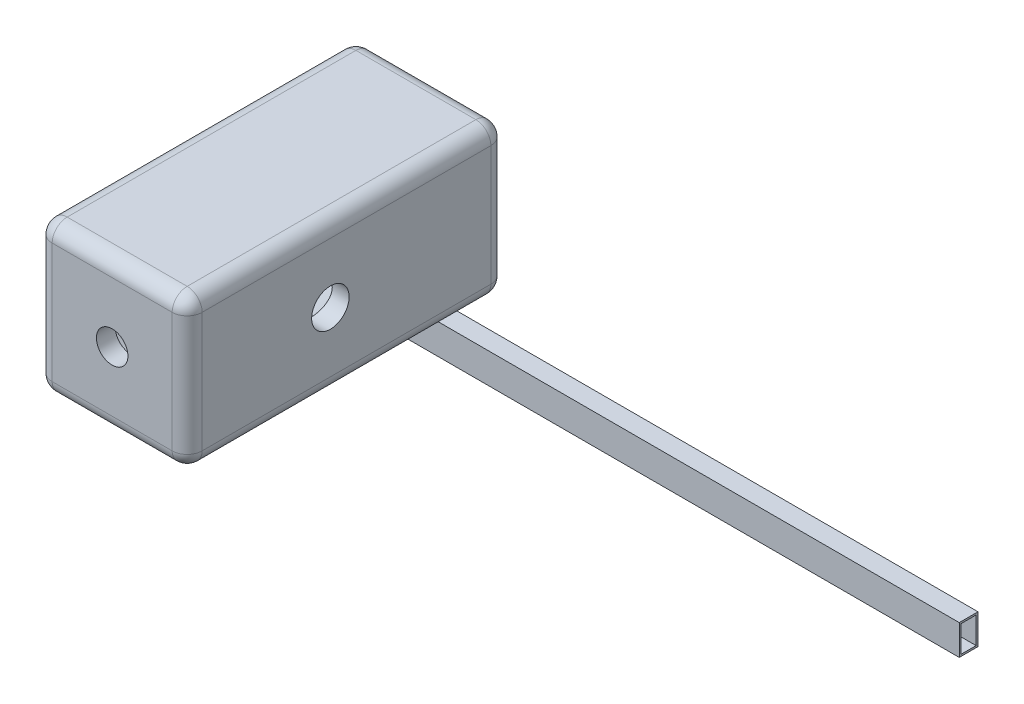
SolidWorks part; units mm, degrees
ref_plane "Front Plane" through (0, 0, 0) normal (0, 0, 1) x (1, 0, 0)
ref_plane "Top Plane" through (0, 0, 0) normal (0, 1, 0) x (1, 0, 0)
ref_plane "Right Plane" through (0, 0, 0) normal (1, 0, 0) x (0, 0, -1)
sketch "Sketch1" plane through (0, 0, 0) normal (0, 0, 1) x (1, 0, 0)
  line L1 (-25.4, 25.4) -> (25.4, 25.4)
  line L2 (-25.4, 25.4) -> (-25.4, -25.4)
  line L3 (-25.4, -25.4) -> (25.4, -25.4)
  line L4 (25.4, 25.4) -> (25.4, -25.4)
  line L5 (-25.4, 25.4) -> (25.4, -25.4) construction
  line L6 (-25.4, -25.4) -> (25.4, 25.4) construction
  point P0 (0, 0)
extrude "Boss-Extrude1" add sketch "Sketch1" against normal blind 101.6
sketch "Sketch3" plane through (0, 0, 0) normal (0, 0, 1) x (1, 0, 0)
  circle A0 centre (0, 0) radius 19.685
extrude "Cut-Extrude1" cut sketch "Sketch3" against normal blind 88.9 contours A0
sketch "Sketch6" plane through (0, 0, -101.6) normal (0, 0, -1) x (-1, 0, 0)
  line L1 (-7.62, 0) -> (-7.62, -25.4048)
  line L2 (7.62, 0) -> (7.62, -25.4048)
  line L5 (-7.62, -25.4048) -> (-7.62, -31.7548)
  line L6 (7.62, -25.4048) -> (7.62, -31.7548)
  line L7 (-7.62, -31.7548) -> (7.62, -31.7548)
  arc A0 (7.62, 0) -> (-7.62, 0) centre (0, 0) ccw
extrude "Boss-Extrude2" add sketch "Sketch6" along normal blind 10.16
sketch "Sketch11" plane through (0, 0, -88.9) normal (0, 0, 1) x (1, 0, 0)
  circle A0 centre (0, 0) radius 6.35
extrude "Cut-Extrude3" cut sketch "Sketch11" against normal blind 20.32
sketch "Sketch13" plane through (0, 0, 0) normal (0, 0, 1) x (1, 0, 0)
  line L1 (-25.4, 25.4) -> (25.4, 25.4)
  line L2 (-25.4, 25.4) -> (-25.4, -25.4)
  line L3 (-25.4, -25.4) -> (25.4, -25.4)
  line L4 (25.4, 25.4) -> (25.4, -25.4)
  circle A0 centre (0, 0) radius 5.334
extrude "Boss-Extrude4" add sketch "Sketch13" along normal blind 6.35
fillet "Fillet2" radius 5.08 4 edges at (-25.4, 0, -101.6) (-25.4, 25.4, -47.625) (-25.4, 0, 6.35) (-25.4, -25.4, -47.625)
fillet "Fillet5" radius 2.54 3 edges at (0, 7.62, -111.76) (7.62, -15.8774, -111.76) (-7.62, -15.8774, -111.76)
sketch "Sketch14" plane through (-25.4, 0, 0) normal (-1, 0, 0) x (0, 0, 1)
  line L0 (6.35, 25.4) -> (6.35, -25.4) construction
  circle A0 centre (-42.164, 0) radius 6.35
  dimension "D1" = 48.514
extrude "Cut-Extrude5" cut sketch "Sketch14" against normal through all both and the other way through all
fillet "Fillet8" radius 5.08 6 edges at (25.4, 0, -101.6) (2.54, -25.4, 6.35) (-23.9121, -23.9121, 4.8621) (-23.9121, 23.9121, -100.1121) (25.4, -25.4, -47.625) (2.54, 25.4, -101.6)
fillet "Fillet10" radius 5.08 4 edges at (23.9121, -23.9121, 4.8621) (2.54, 25.4, 6.35) (-23.9121, 23.9121, 4.8621) (25.4, 2.54, 6.35)
fillet "Fillet11" radius 5.08 3 edges at (25.4, 25.4, -47.625) (23.9121, 23.9121, -100.1121) (23.9121, 23.9121, 4.8621)
fillet "Fillet12" radius 5.08 2 edges at (-13.97, -25.4, -101.6) (-23.9121, -23.9121, -100.1121)
fillet "Fillet13" radius 5.08 2 edges at (23.9121, -23.9121, -100.1121) (13.97, -25.4, -101.6)
sketch "Sketch16" plane through (0, -31.7548, 0) normal (0, -1, 0) x (1, 0, 0)
  line L1 (-5.261, -103.9976) -> (5.261, -103.9976)
  line L2 (-5.261, -103.9976) -> (-5.261, -109.3779)
  line L3 (-5.261, -109.3779) -> (5.261, -109.3779)
  line L4 (5.261, -103.9976) -> (5.261, -109.3779)
  line L5 (-5.261, -103.9976) -> (5.261, -109.3779) construction
  line L6 (-5.261, -109.3779) -> (5.261, -103.9976) construction
  point P0 (0, -106.6877)
  point P2 (0.5015, -106.4568)
  point P6 (0, 0)
  point P7 (-0.5849, -106.4051)
  point P8 (0, 0)
  point P9 (0, 0)
  point P10 (0.8119, -106.7155)
  point P11 (0, -106.6877)
extrude "Cut-Extrude6" cut sketch "Sketch16" against normal blind 33.02
sketch "Sketch23" plane through (0, -31.7548, 0) normal (0, -1, 0) x (1, 0, 0)
  line L1 (-7.62, -101.6) -> (7.62, -101.6)
  line L2 (-7.62, -101.6) -> (-7.62, -111.7263)
  line L3 (7.62, -101.6) -> (7.62, -111.7263)
  line L4 (-7.62, -111.7263) -> (7.62, -111.7263)
extrude "Boss-Extrude8" add sketch "Sketch23" along normal blind 3.81
fillet "Fillet18" radius 2.54 1 edges at (7.62, -33.6598, -111.7263)
fillet "Fillet19" radius 2.54 1 edges at (-7.62, -33.6598, -111.7263)
sketch "Sketch24" plane through (0, 0, -101.6) normal (0, 0, 1) x (1, 0, 0)
  line L0 (-7.62, -25.4) -> (7.62, -25.4)
  line L1 (-7.62, -25.4) -> (-7.62, -35.65)
  line L2 (7.62, -25.4) -> (7.62, -35.65)
  line L3 (-7.62, -35.65) -> (7.62, -35.65)
extrude "Boss-Extrude9" add sketch "Sketch24" along normal blind 25.4
sketch "Sketch25" plane through (0, 0, -76.2) normal (0, 0, 1) x (1, 0, 0)
  line L1 (-5.1671, -27.4415) -> (5.1671, -27.4415)
  line L2 (-5.1671, -27.4415) -> (-5.1671, -34.0251)
  line L3 (-5.1671, -34.0251) -> (5.1671, -34.0251)
  line L4 (5.1671, -27.4415) -> (5.1671, -34.0251)
  line L5 (-5.1671, -27.4415) -> (5.1671, -34.0251) construction
  line L6 (-5.1671, -34.0251) -> (5.1671, -27.4415) construction
  point P0 (0, -30.7333)
extrude "Cut-Extrude9" cut sketch "Sketch25" against normal blind 33.02
sketch "Sketch26" plane through (0, 0, -76.2) normal (0, 0, 1) x (1, 0, 0)
  line L1 (-7.62, -25.4) -> (7.62, -25.4)
  line L2 (-7.62, -25.4) -> (-7.62, -35.65)
  line L3 (-7.62, -35.65) -> (7.62, -35.65)
  line L4 (7.62, -25.4) -> (7.62, -35.65)
extrude "Boss-Extrude10" add sketch "Sketch26" along normal blind 6.35
sketch "Sketch27" plane through (7.62, 0, 0) normal (1, 0, 0) x (0, 0, -1)
  line L0 (69.85, -35.65) -> (101.6, -35.65) construction
  line L1 (81.6815, -25.4235) -> (88.0315, -25.4235)
  line L2 (81.6815, -25.4235) -> (81.6815, -35.65)
  line L3 (81.6815, -35.65) -> (88.0315, -35.65)
  line L4 (88.0315, -25.4235) -> (88.0315, -35.65)
  line L5 (81.6815, -25.4235) -> (88.0315, -35.65) construction
  line L6 (81.6815, -35.65) -> (88.0315, -25.4235) construction
  line L12 (82.3141, -26.0416) -> (87.3988, -26.0416)
  line L13 (82.3141, -26.0416) -> (82.3141, -35.0319)
  line L14 (82.3141, -35.0319) -> (87.3988, -35.0319)
  line L15 (87.3988, -26.0416) -> (87.3988, -35.0319)
  line L16 (82.3141, -26.0416) -> (87.3988, -35.0319) construction
  line L17 (82.3141, -35.0319) -> (87.3988, -26.0416) construction
  point P0 (84.8565, -30.5367)
  point P7 (84.8565, -30.5367)
  point P8 (84.8565, -30.5367)
extrude "Boss-Extrude11" add sketch "Sketch27" along normal blind 191.262
sketch "Sketch28" plane through (7.62, 0, 0) normal (1, 0, 0) x (0, 0, -1)
  line L5 (82.3141, -26.0416) -> (87.3988, -26.0416)
  line L6 (82.3141, -26.0416) -> (82.3141, -35.0319)
  line L7 (82.3141, -35.0319) -> (87.3988, -35.0319)
  line L8 (87.3988, -26.0416) -> (87.3988, -35.0319)
extrude "Cut-Extrude10" cut sketch "Sketch28" against normal blind 6.35
